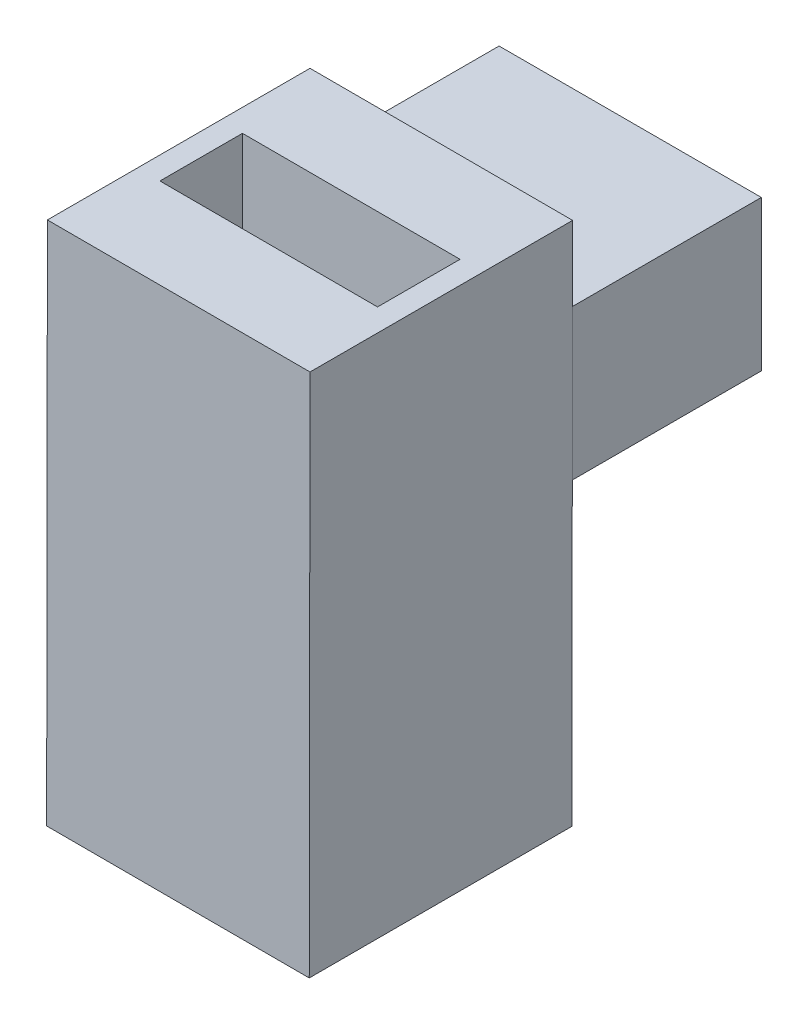
SolidWorks part; units mm, degrees
ref_plane "Front" through (0, 0, 0) normal (0, 0, 1) x (1, 0, 0)
ref_plane "Top" through (0, 0, 0) normal (0, 1, 0) x (1, 0, 0)
ref_plane "Right" through (0, 0, 0) normal (1, 0, 0) x (0, 0, -1)
sketch "Sketch3" plane through (0, 96.8586, 4.3621) normal (-0.0014, -1, 0) x (1, -0.0014, 0)
  line L1 (-8.75, -9.7077) -> (8.75, -9.7077)
  line L2 (-8.75, -9.7077) -> (-8.75, 7.7923)
  line L3 (-8.75, 7.7923) -> (8.75, 7.7923)
  line L4 (8.75, -9.7077) -> (8.75, 7.7923)
  line L5 (-8.75, -9.7077) -> (8.75, 7.7923) construction
  line L6 (-8.75, 7.7923) -> (8.75, -9.7077) construction
  circle A0 centre (0, -0.9577) radius 6.75
  circle A1 centre (0, -0.9577) radius 8.75 construction
  dimension "D1" = 13.5
  dimension "D2" = 2
extrude "Boss-Extrude2" add sketch "Sketch3" along normal blind 20 separate body
sketch "Sketch1" plane through (0, 0, -5.3455) normal (0, 0, 1) x (1, 0, 0)
  line L0 (-2.24, 103.1286) -> (2.24, 103.1286)
  line L2 (-8.7281, 96.8711) -> (8.75, 96.8461)
  line L3 (-8.7281, 96.8711) -> (-8.7281, 106.8586)
  line L4 (-8.7281, 106.8586) -> (8.75, 106.8586)
  line L5 (8.75, 96.8461) -> (8.75, 106.8586)
  line L6 (-8.7281, 96.8711) -> (8.75, 106.8586) construction
  line L7 (-8.7281, 106.8586) -> (8.75, 96.8461) construction
  line L13 (8.75, 96.8461) -> (-8.75, 96.8711) construction
  line L14 (8.75, 96.8461) -> (-8.75, 96.8711) construction
  arc A0 (-2.24, 103.1286) -> (2.24, 103.1286) centre (0, 101.8586) ccw
  circle A2 centre (0, 101.8586) radius 1.5 construction
  arc A3 (2.24, 103.1286) -> (-2.24, 103.1286) centre (0, 101.8586) ccw construction
  circle A4 centre (0, 101.8586) radius 5 construction
  dimension "D1" = 5.15
  dimension "D3" = 10
  dimension "D2" = 4.48
extrude "Boss-Extrude1" add sketch "Sketch1" against normal blind 12.6
sketch "Sketch4" plane through (-0.0693, 96.8587, 0) normal (-0.0014, -1, 0) x (-1, 0.0014, 0)
  line L1 (-7.3193, -6.1545) -> (7.1807, -6.1545)
  line L2 (-7.3193, -6.1545) -> (-7.3193, -0.6545)
  line L3 (-7.3193, -0.6545) -> (7.1807, -0.6545)
  line L4 (7.1807, -6.1545) -> (7.1807, -0.6545)
  line L5 (-7.3193, -6.1545) -> (7.1807, -0.6545) construction
  line L6 (-7.3193, -0.6545) -> (7.1807, -6.1545) construction
  line L10 (-8.8193, 5.3455) -> (-8.8193, -12.1545)
  line L11 (8.6807, 5.3455) -> (-8.8193, 5.3455)
  line L12 (8.6807, -12.1545) -> (8.6807, 5.3455)
  line L13 (-8.8193, -12.1545) -> (8.6807, -12.1545)
  line L14 (6.9307, -0.9045) -> (-7.0693, -0.9045) construction
  line L15 (-7.0693, -0.9045) -> (-7.0693, -5.9045) construction
  line L16 (-7.0693, -5.9045) -> (6.9307, -5.9045) construction
  line L17 (6.9307, -5.9045) -> (6.9307, -0.9045) construction
  line L18 (-8.8193, 5.3455) -> (-8.8193, -12.1545)
  line L19 (8.6807, 5.3455) -> (-8.8193, 5.3455)
  line L20 (8.6807, -12.1545) -> (8.6807, 5.3455)
  line L21 (-8.8193, -12.1545) -> (8.6807, -12.1545)
  circle A2 centre (-0.0693, -3.4045) radius 6.75 construction
  circle A3 centre (-0.0693, -3.4045) radius 6.75 construction
  dimension "D1" = 0.25
  dimension "D2" = 0.25
  dimension "D3" = 0.25
  dimension "D4" = 0.25
  dimension "D5" = 0
extrude "Boss-Extrude3" add sketch "Sketch4" against normal blind 15
sketch "Sketch2" plane through (0, 0, -17.9455) normal (0, 0, -1) x (-1, 0, 0)
  line L0 (-8.75, 106.8586) -> (8.7281, 106.8586) construction
  line L1 (-8.75, 96.8461) -> (-8.75, 106.8586) construction
  circle A0 centre (0, 101.8586) radius 2.575
  dimension "D1" = 5.15
  dimension "D2" = 5
  dimension "D3" = 8.75
extrude "Cut-Extrude1" cut sketch "Sketch2" against normal blind 5
sketch "Sketch5" plane through (0, 0, -17.9455) normal (0, 0, -1) x (-1, 0, 0)
  line L1 (-1.5906, 103.8836) -> (1.5906, 103.8836)
  line L2 (0, 103.8836) -> (0, 99.2836) construction
  line L4 (1.5906, 103.8836) -> (-1.5906, 103.8836)
  arc A0 (-1.5906, 103.8836) -> (1.5906, 103.8836) centre (0, 101.8586) ccw
  arc A2 (1.5906, 103.8836) -> (-1.5906, 103.8836) centre (0, 101.8586) ccw construction
  point P6 (0, 0)
  point P7 (0, 0)
  circle M7 centre (0, 101.8586) radius 2.575
  dimension "D1" = 5.15
  dimension "D2" = 4.6
extrude "Cut-Extrude2" cut sketch "Sketch5" against normal up to surface (18.6 mm away) contours L1 M7 region at (0, 101.722, -17.9455) up to face at (0.0072, 101.8586, 0.6545)
